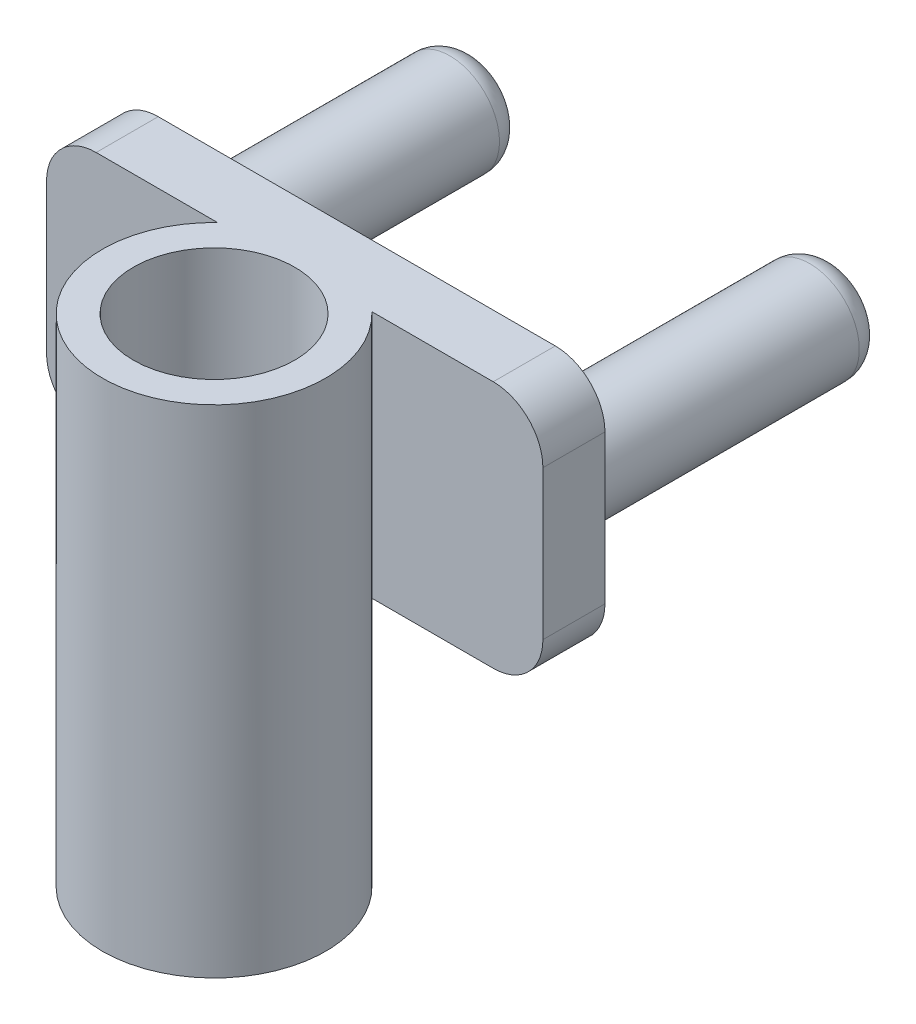
SolidWorks part; units mm, degrees
ref_plane "Front Plane" through (0, 0, 0) normal (0, 0, 1) x (1, 0, 0)
ref_plane "Top Plane" through (0, 0, 0) normal (0, 1, 0) x (1, 0, 0)
ref_plane "Right Plane" through (0, 0, 0) normal (1, 0, 0) x (0, 0, -1)
sketch "Sketch1" plane through (0, 0, 0) normal (0, 1, 0) x (1, 0, 0)
  circle A0 centre (0, 0) radius 3.25
  circle A1 centre (0, 0) radius 4.5
  dimension "D1" = 6.5
  dimension "D2" = 9
extrude "Boss-Extrude1" add sketch "Sketch1" along normal blind 20
ref_plane "Plane1" through (0, 0, -4.5) normal (0, 0, 1) x (1, 0, 0)
sketch "Sketch2" plane through (0, 0, -4.5) normal (0, 0, 1) x (1, 0, 0)
  line L0 (-4.5, 10) -> (4.5, 10) construction
  line L1 (-4.5, 20) -> (-4.5, 0) construction
  line L2 (4.5, 0) -> (4.5, 20) construction
  line L3 (0, 10) -> (0, 15) construction
  line L4 (-10, 20) -> (-4.5, 10) construction
  line L5 (-10, 20) -> (10, 20)
  line L6 (-10, 20) -> (-10, 10)
  line L7 (-10, 10) -> (10, 10)
  line L8 (10, 20) -> (10, 10)
  line L9 (-10, 20) -> (10, 10) construction
  line L10 (-10, 10) -> (10, 20) construction
  line L11 (4.5, 10) -> (10, 20) construction
  circle A0 centre (-7.25, 15) radius 2
  circle A1 centre (7.25, 15) radius 2
  dimension "D4" = 4
  dimension "D1" = 5
  dimension "D2" = 10
  dimension "D3" = 20
extrude "Boss-Extrude2" add sketch "Sketch2" along normal mid plane 2.5 contours L6 L5 L8 L7
fillet "Fillet1" radius 2 4 edges at (-10, 10, -4.5) (-10, 20, -4.5) (10, 10, -4.5) (10, 20, -4.5)
sketch "Sketch3" plane through (0, 0, -5.75) normal (0, 0, -1) x (-1, 0, 0)
  circle A2 centre (-7.25, 15) radius 2 construction
  circle A3 centre (-7.25, 15) radius 2
extrude "Boss-Extrude3" add sketch "Sketch3" along normal blind 12
ref_axis "Axis1" through (7.25, 15, -17.75) along (0, 0, 1)
ref_plane "Plane2" through (0, 15, 0) normal (0, 1, 0) x (0, 0, 1)
sketch "Sketch4" plane through (0, 15, 0) normal (0, 1, 0) x (0, 0, 1)
  line L0 (-17.75, 7.25) -> (-5.75, 7.25) construction
  line L1 (-17.75, 9.25) -> (-17.75, 5.25) construction
  line L3 (-17.75, 6.35) -> (-16.4127, 5.274)
  line L4 (-16.25, 5.3519) -> (-16.25, 5.75)
  line L5 (-16.15, 5.85) -> (-15.55, 5.85)
  line L6 (-15.45, 5.75) -> (-15.45, 5.45)
  line L7 (-15.35, 5.35) -> (-5.75, 5.35)
  line L8 (-5.75, 5.35) -> (-5.75, 4.85)
  line L9 (-5.75, -8) -> (-5.75, 8) construction
  line L10 (-5.75, 4.85) -> (-17.75, 4.85)
  line L11 (-17.75, 4.85) -> (-17.75, 6.35)
  line L12 (-17.75, 5.25) -> (-5.75, 5.25) construction
  arc A0 (-15.45, 5.45) -> (-15.35, 5.35) centre (-15.35, 5.45) ccw
  arc A1 (-15.55, 5.85) -> (-15.45, 5.75) centre (-15.55, 5.75) cw
  arc A2 (-16.25, 5.75) -> (-16.15, 5.85) centre (-16.15, 5.75) cw
  arc A3 (-16.4127, 5.274) -> (-16.25, 5.3519) centre (-16.35, 5.3519) ccw
  dimension "D1" = 0.1
  dimension "D7" = 1.5
  dimension "D2" = 10.5
  dimension "D3" = 9.7
  dimension "D4" = 0.6
  dimension "D5" = 0.1
  dimension "D6" = 0.4
  dimension "D8" = 1.3373
revolve "Cut-Revolve2" [suppressed] cut sketch "Sketch4" angle 360 about L0
sketch "Sketch5" [suppressed] plane through (0, 0, -17.75) normal (0, 0, -1) x (-1, 0, 0)
  line L0 (-7.25, 15) -> (-7.25, 16.976) construction
  line L2 (-7.35, 12.9597) -> (-7.15, 12.9597)
  line L3 (-7.35, 12.9597) -> (-7.35, 17.0403)
  line L4 (-7.35, 17.0403) -> (-7.15, 17.0403)
  line L5 (-7.15, 12.9597) -> (-7.15, 17.0403)
  line L6 (-7.35, 12.9597) -> (-7.15, 17.0403) construction
  line L7 (-7.35, 17.0403) -> (-7.15, 12.9597) construction
  circle A0 centre (-7.25, 15) radius 1.976 construction
  dimension "D1" = 0.2
extrude "Cut-Extrude1" [suppressed] cut sketch "Sketch5" against normal blind 10
pattern_linear "LPattern3" count 2 spacing 14.5 along (-1, 0, 0) of "Cut-Revolve2", "Cut-Extrude1", "Boss-Extrude3"
fillet "Fillet2" radius 1 2 edges at (-9.25, 15, -17.75) (5.25, 15, -17.75)
